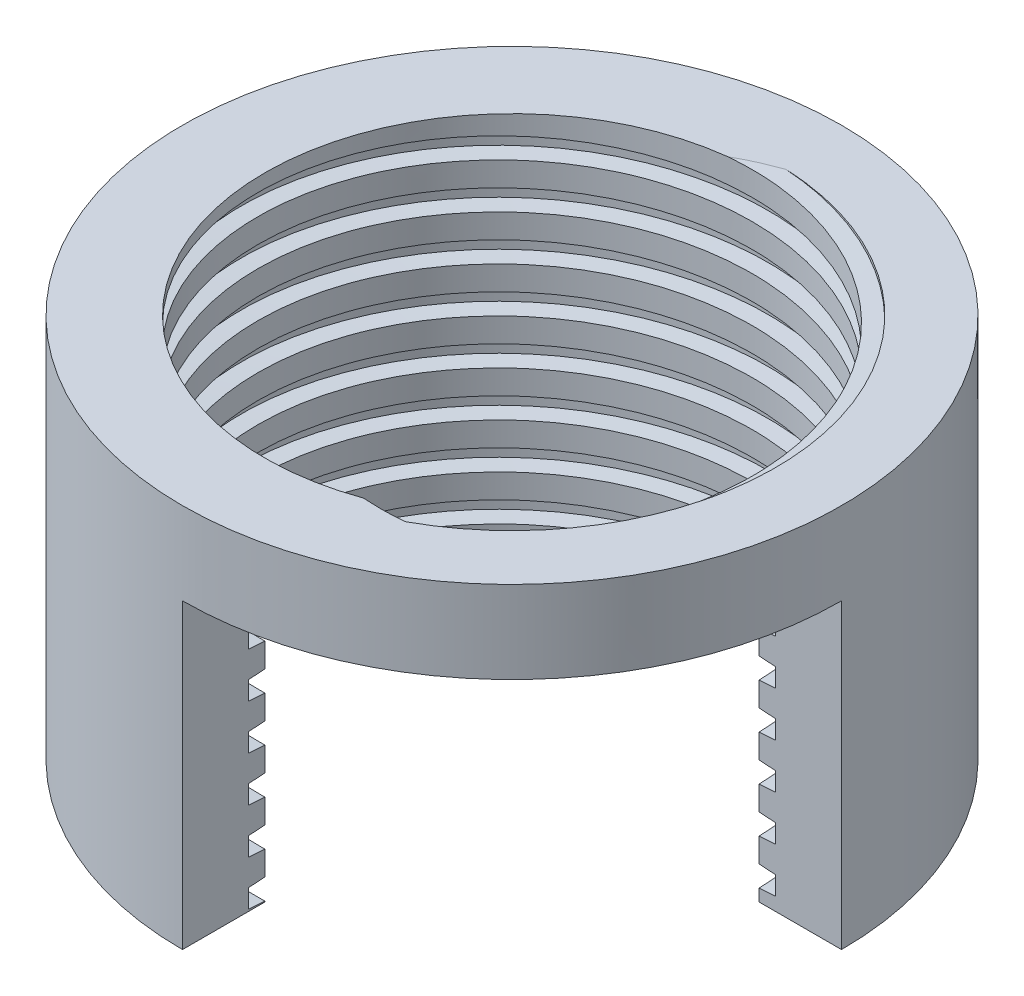
SolidWorks part; units mm, degrees
ref_plane "Front Plane" through (0, 0, 0) normal (0, 0, 1) x (1, 0, 0)
ref_plane "Top Plane" through (0, 0, 0) normal (0, 1, 0) x (1, 0, 0)
ref_plane "Right Plane" through (0, 0, 0) normal (1, 0, 0) x (0, 0, -1)
sketch "Sketch2" plane through (0, 0, 0) normal (0, 1, 0) x (1, 0, 0)
  circle A0 centre (0, 0) radius 4.5
  circle A1 centre (0, 0) radius 6
  dimension "D1" = 9
  dimension "D2" = 1.5
extrude "Boss-Extrude1" add sketch "Sketch2" along normal blind 7
sketch "Sketch3" plane through (0, 0, 0) normal (0, 0, 1) x (1, 0, 0)
  line L0 (-4.5, 0) -> (-4.8, 0) construction
  line L1 (-4.5, 0) -> (4.5, 0) construction
  line L2 (-4.8, -0.17) -> (-4.8, 0.17)
  line L3 (-4.8, 0.17) -> (-4.5, 0.19)
  line L4 (-4.5, 0.19) -> (-4.5, -0.19)
  line L5 (-4.8, -0.17) -> (-4.5, -0.19)
  dimension "D1" = 4.8
  dimension "D2" = 0.34
  dimension "D3" = 0.38
sketch "Sketch5" plane through (0, 0, 0) normal (0, 1, 0) x (1, 0, 0)
  circle A0 centre (0, 0) radius 4.5 construction
  circle A1 centre (0, 0) radius 4.5
curve "Helix/Spiral1" pitch 0.82 height 7 radius 4.5 centre (0, 0, 0) axis (0, 1, 0) start towards (0, 0, 1)
sweep "Cut-Sweep1" cut profiles "Sketch3" path "Helix/Spiral1" align with end faces yes
sketch "Sketch6" plane through (0, 0, 0) normal (0, 1, 0) x (1, 0, 0)
  line L0 (0, 0) -> (7, 0)
  line L1 (0, 0) -> (0, -7)
  arc A0 (7, 0) -> (0, -7) centre (0, 0) cw
  point P6 (0, 0)
  dimension "D1" = 7
extrude "cutout" cut sketch "Sketch6" along normal blind 5.5
